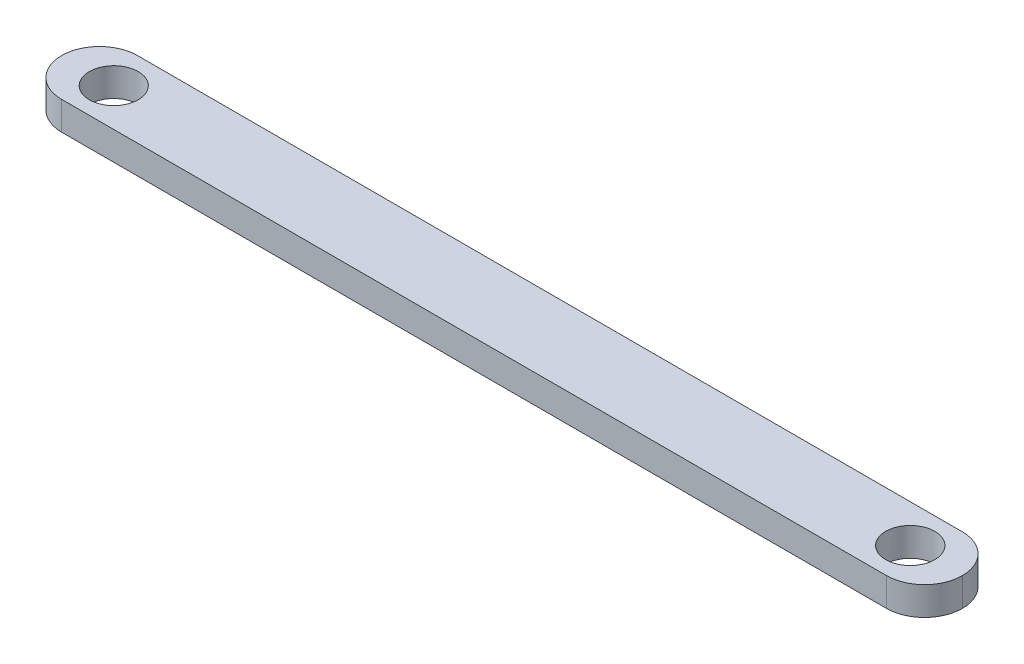
SolidWorks part; units mm, degrees
ref_plane "Front Plane" through (0, 0, 0) normal (0, 0, 1) x (1, 0, 0)
ref_plane "Top Plane" through (0, 0, 0) normal (0, 1, 0) x (1, 0, 0)
ref_plane "Right Plane" through (0, 0, 0) normal (1, 0, 0) x (0, 0, -1)
sketch "Sketch1" plane through (0, 0, 0) normal (0, 1, 0) x (1, 0, 0)
  line L0 (-47.6, 1.5) -> (47.4, 1.5) construction
  line L1 (-47.6, -2.5) -> (47.4, -2.5)
  line L2 (-47.6, -2.5) -> (-47.6, 5.5)
  line L3 (-47.6, 5.5) -> (47.4, 5.5)
  line L4 (47.4, -2.5) -> (47.4, 5.5)
  line L7 (-0.1, 5.5) -> (-0.1, -2.5) construction
  line L8 (-42.1, 5.5) -> (-42.1, -2.5) construction
  line L9 (41.9, 5.5) -> (41.9, -2.5) construction
  circle A0 centre (-42.1, 1.5) radius 2.58
  circle A1 centre (41.9, 1.5) radius 2.59
  point P0 (0, 0)
  dimension "D1" = 5.5
  dimension "D2" = 8
  dimension "D3" = 84
  dimension "D4" = 5.5
extrude "Boss-Extrude1" add sketch "Sketch1" along normal blind 3
fillet "Redondeo2" radius 4 4 edges at (47.4, 1.5, -5.5) (47.4, 1.5, 2.5) (-47.6, 1.5, -5.5) (-47.6, 1.5, 2.5)
